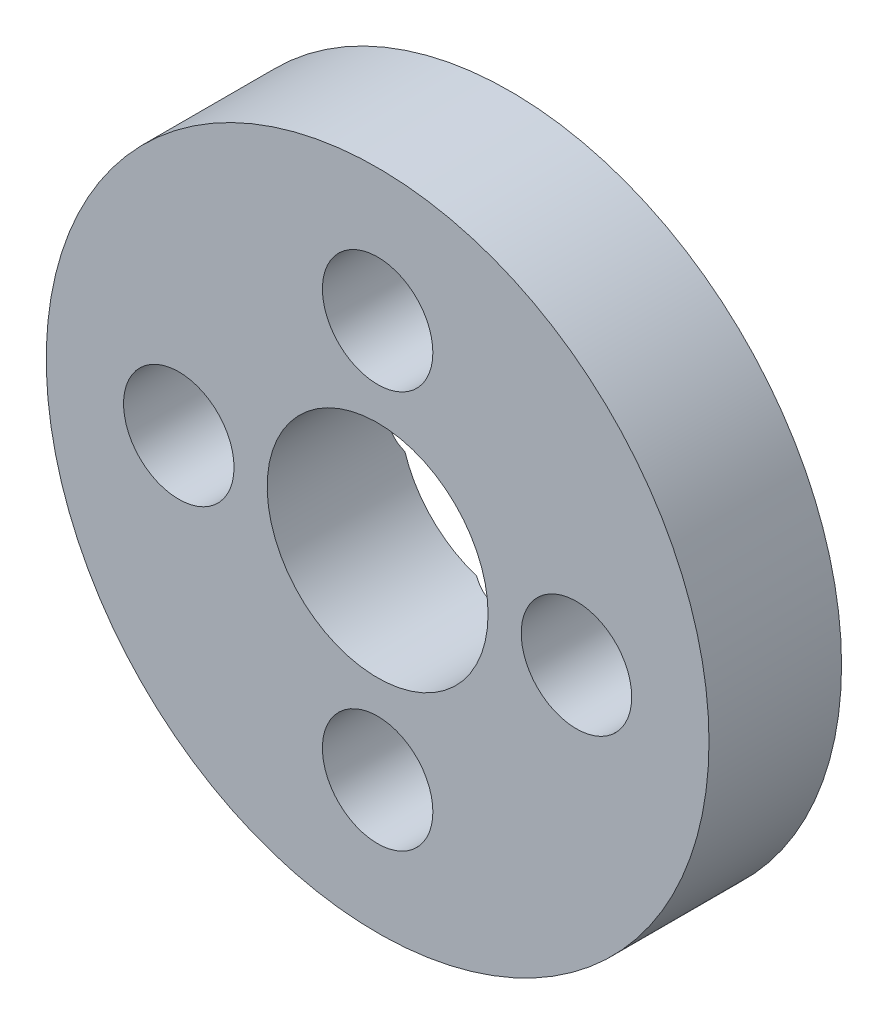
SolidWorks part; units mm, degrees
ref_plane "前视基准面" through (0, 0, 0) normal (0, 0, 1) x (1, 0, 0)
ref_plane "上视基准面" through (0, 0, 0) normal (0, 1, 0) x (1, 0, 0)
ref_plane "右视基准面" through (0, 0, 0) normal (1, 0, 0) x (0, 0, -1)
other "Configuration Table"
sketch "草图1" plane through (0, 0, 0) normal (0, 0, 1) x (1, 0, 0)
  circle A0 centre (0, 0) radius 2.5
  circle A1 centre (0, 0) radius 7.5
  dimension "D1" = 5
  dimension "D2" = 15
extrude "凸台-拉伸1" add sketch "草图1" along normal blind 3
sketch "草图2" plane through (0, 0, 3) normal (0, 0, 1) x (1, 0, 0)
  circle A0 centre (0, 0) radius 4.5 construction
  circle A1 centre (0, 4.5) radius 1.25
  circle A5 centre (4.5, 0) radius 1.25
  circle A6 centre (0, -4.5) radius 1.25
  circle A7 centre (-4.5, 0) radius 1.25
  point P5 (0, 0)
  point P6 (0, 0)
  point P14 (-0.125, 0.125)
  point P15 (0, 0)
  dimension "D1" = 9
  dimension "D2" = 2.5
  dimension "D3" = 4
extrude "切除-拉伸1" cut sketch "草图2" against normal blind 10
chamfer "倒角1" distance 1 angle 45 4 edges at (-3.25, 0, 0) (1.25, -4.5, 0) (5.75, 0, 0) (1.25, 4.5, 0)
